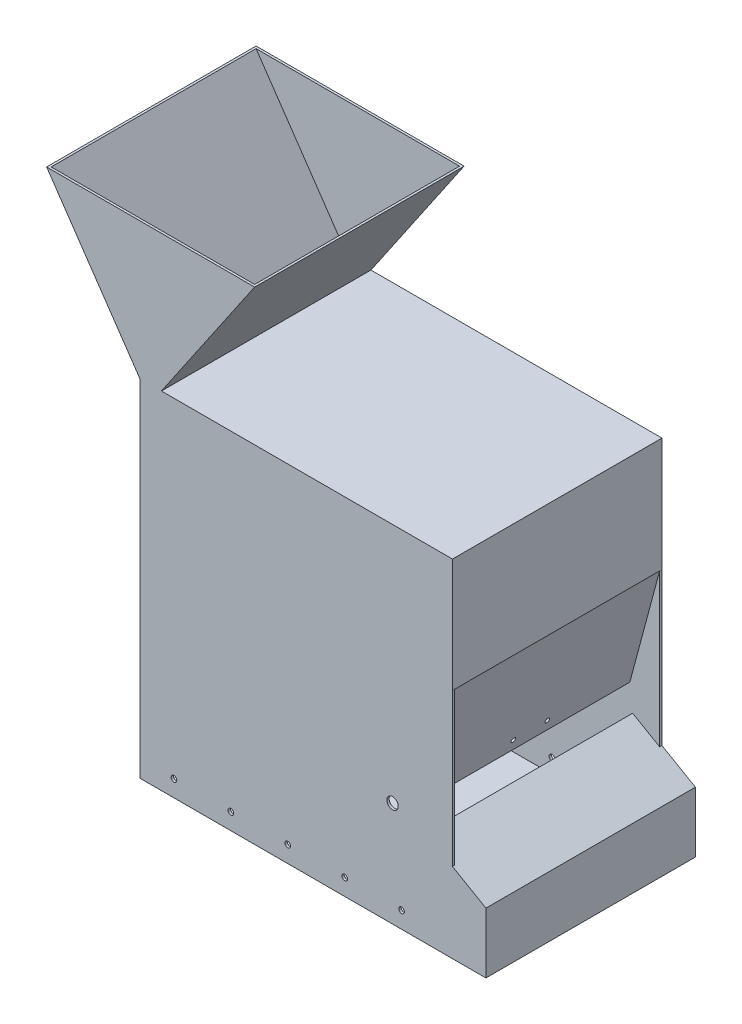
SolidWorks part; units mm, degrees
ref_plane "前视基准面" through (0, 0, 0) normal (0, 0, 1) x (1, 0, 0)
ref_plane "上视基准面" through (0, 0, 0) normal (0, 1, 0) x (1, 0, 0)
ref_plane "右视基准面" through (0, 0, 0) normal (1, 0, 0) x (0, 0, -1)
sketch "草图1" plane through (0, 0, 0) normal (0, 0, 1) x (1, 0, 0)
  line L0 (0, 0) -> (0, 200)
  line L1 (0, 200) -> (270, 200)
  line L3 (248.2424, 79.8823) -> (300, 50)
  line L4 (300, 50) -> (300, 0)
  line L5 (300, 0) -> (0, 0)
  line L7 (-2, 202) -> (272.6065, 202)
  line L9 (270, 200) -> (244.9779, 106.6164)
  line L10 (-2, 202) -> (-2, -2)
  line L11 (-2, -2) -> (302, -2)
  line L12 (302, -2) -> (302, 51.1547)
  line L13 (302, 51.1547) -> (248.8665, 81.8314)
  line L14 (272.6065, 202) -> (246.4095, 104.2316)
  circle A0 centre (220, 90) radius 30
  dimension "D6" = 60
  dimension "D1" = 300
  dimension "D2" = 200
  dimension "D3" = 50
  dimension "D4" = 30
  dimension "D5" = 270
  dimension "D7" = 110
  dimension "225" = 220
  dimension "D8" = 2
  dimension "D9" = 75
  dimension "D10" = 2
  dimension "D11" = 2
  dimension "D12" = 2
  dimension "D13" = 2
  dimension "D14" = 2
extrude "凸台-拉伸3" add sketch "草图1" along normal blind 180 contours A0 L7 L10 L11 L12 L13 L3 L4 L5 L0 L1 region at (150, -0.3661, 0)
sketch "草图7" plane through (0, 0, 0) normal (0, 0, -1) x (-1, 0, 0)
  line L1 (-302, 51.1547) -> (-248.8665, 81.8314) construction
  line L2 (-275.4332, 66.493) -> (-302, 51.1547)
  line L3 (-302, 51.1547) -> (-302, -2)
  line L4 (-302, -2) -> (2, -2)
  line L5 (2, -2) -> (2, 202)
  line L7 (2, 202) -> (-272.6065, 202)
  line L8 (-272.6065, 202) -> (-272.6065, 68.1251)
  line L9 (-272.6065, 68.1251) -> (-275.4332, 66.493)
extrude "凸台-拉伸4" add sketch "草图7" along normal blind 2
ref_plane "基准面3" through (0, 0, 90) normal (0, 0, 1) x (1, 0, 0)
mirror "镜向5" about plane through (0, 0, 90) normal (0, 0, 1) of "凸台-拉伸4"
sketch "草图8" plane through (0, 0, 0) normal (0, 0, 1) x (1, 0, 0)
  line L1 (-2, 202) -> (272.6065, 202) construction
  line L2 (-2, 202) -> (-2, -2) construction
  line L3 (-2, -2) -> (302, -2) construction
  line L4 (302, -2) -> (302, 51.1547) construction
  line L5 (302, 51.1547) -> (248.8665, 81.8314) construction
  line L7 (0, 200) -> (270, 200) construction
  line L8 (0, 0) -> (0, 200) construction
  line L9 (300, 0) -> (0, 0) construction
  line L10 (300, 50) -> (300, 0) construction
  line L11 (248.2424, 79.8823) -> (300, 50) construction
  line L13 (-2, 202) -> (272.6065, 202) construction
  line L14 (-2, 202) -> (-2, -2) construction
  line L15 (-2, -2) -> (302, -2) construction
  line L16 (302, -2) -> (302, 51.1547) construction
  line L17 (302, 51.1547) -> (248.8665, 81.8314) construction
  line L19 (0, 200) -> (270, 200)
  line L20 (0, 0) -> (0, 200) construction
  line L21 (300, 0) -> (0, 0) construction
  line L22 (300, 50) -> (300, 0) construction
  line L23 (248.2424, 79.8823) -> (300, 50) construction
  line L24 (220, 135.3561) -> (220, 31.0609) construction
  line L25 (165.6053, 90) -> (270, 90) construction
  line L26 (212.2354, 118.9778) -> (220, 90) construction
  line L27 (227.7646, 118.9778) -> (220, 90) construction
  line L28 (248.9778, 97.7646) -> (220, 90) construction
  line L29 (241.2132, 111.2132) -> (220, 90) construction
  line L30 (241.2132, 68.7868) -> (220, 90) construction
  line L31 (248.9778, 82.2354) -> (220, 90) construction
  line L32 (212.2354, 61.0222) -> (220, 90) construction
  line L33 (227.7646, 61.0222) -> (220, 90) construction
  line L34 (191.0222, 82.2354) -> (220, 90) construction
  line L35 (198.7868, 68.7868) -> (220, 90) construction
  line L36 (198.7868, 111.2132) -> (220, 90) construction
  line L37 (191.0222, 97.7646) -> (220, 90) construction
  line L38 (191.0222, 97.7646) -> (0, 144.3277)
  line L39 (0, 0) -> (0, 200) construction
  line L40 (0, 140.3998) -> (190.2705, 94.0199)
  line L41 (270, 200) -> (270.631, 202)
  line L42 (270.631, 202) -> (0, 202)
  line L43 (0, 202) -> (0, 200)
  circle A0 centre (220, 90) radius 30
  circle A1 centre (220, 90) radius 30
  circle A2 centre (220, 90) radius 30 construction
  point P36 (220, 90)
  line M26 (0, 200) -> (0, 0)
  dimension "D4" = 60
  dimension "D2" = 30
  dimension "D1" = 0
  dimension "D3" = 6
extrude "凸台-拉伸5" add sketch "草图8" along normal blind 180 contours A0 M26 region at (95.3036, 119.1341, 0)
sketch "草图10" plane through (0, 0, 0) normal (0, 0, 1) x (1, 0, 0)
  line L0 (300, 0) -> (0, 0) construction
  line L1 (0, 0) -> (0, 200) construction
  circle A0 centre (60, 60) radius 5
  circle A1 centre (95, 60) radius 6
  dimension "D1" = 10
  dimension "D4" = 35
  dimension "D5" = 12
  dimension "D2" = 60
  dimension "D3" = 60
extrude "切除-拉伸8" cut sketch "草图10" along normal blind 6 and the other way blind 14
extrude "切除-拉伸9" cut sketch "草图8<3>" along normal blind 180 contours L19 L41 L42 L43
sketch "草图8<3>" plane through (0, 0, 0) normal (0, 0, 1) x (1, 0, 0) same geometry as "草图8"
sketch "草图11" plane through (0, 202, 0) normal (0, 1, 0) x (1, 0, 0)
  line L0 (0, 0) -> (270.631, 0)
  line L1 (270.631, 0) -> (270.631, -180)
  line L2 (270.631, -180) -> (0, -180)
  line L3 (0, -180) -> (0, 0)
extrude "拉伸-薄壁1" add sketch "草图11" along normal blind 100 thin thin type one direction wall 2
sketch "草图12" plane through (0, 0, 180) normal (0, 0, -1) x (-1, 0, 0)
  line L0 (-15, 365.8341) -> (-15, 240.3517) construction
  line L1 (0, 144.3277) -> (0, 302) construction
  line L2 (-7.5, 359.5096) -> (-7.5, 254.5421) construction
  line L6 (-98.8691, 422) -> (-96.8691, 422)
  line L9 (-15, 302) -> (-96.8691, 422)
  line L10 (-272.631, 302) -> (2, 302) construction
  line L11 (-15, 302) -> (-17, 302)
  line L12 (-98.8691, 422) -> (-17, 302)
  line L13 (83.8691, 422) -> (81.8691, 422)
  line L14 (0, 302) -> (2, 302)
  line L15 (83.8691, 422) -> (2, 302)
  line L16 (0, 302) -> (81.8691, 422)
  dimension "D1" = 15
  dimension "D2" = 7.5
  dimension "D4" = 120
  dimension "D5" = 2
extrude "凸台-拉伸6" add sketch "草图12" along normal up to surface (90 mm away) and the other way blind 2 up to plane "基准面3"
ref_plane "基准面4" through (0, 0, 182) normal (0, 0, 1) x (1, 0, 0)
sketch "草图16" plane through (0, 0, 182) normal (0, 0, 1) x (1, 0, 0)
  line L0 (-83.8691, 422) -> (98.8691, 422)
  line L1 (98.8691, 422) -> (17, 302)
  line L2 (17, 302) -> (-2, 302)
  line L3 (-2, 302) -> (-83.8691, 422)
extrude "凸台-拉伸12" add sketch "草图16" against normal blind 2
mirror "镜向6" about plane through (0, 0, 90) normal (0, 0, 1) of "镜向5", "凸台-拉伸6"
mirror "镜向7" about plane through (0, 0, 90) normal (0, 0, 1) of "凸台-拉伸12"
sketch "草图17" plane through (0, 0, 180) normal (0, 0, -1) x (-1, 0, 0)
  line L0 (-15, 302) -> (-15, 252)
  line L1 (-15, 365.8341) -> (-15, 240.3517) construction
  line L2 (-15, 252) -> (-10, 232.2686)
  line L3 (-15, 302) -> (-17, 302)
  line L4 (-17, 300) -> (-17, 252)
  line L5 (-17, 252) -> (-11.9009, 231.8774)
  line L6 (-11.9009, 231.8774) -> (-10, 232.2686)
  line L7 (-17, 302) -> (-270.631, 302)
  line L8 (-270.631, 302) -> (-270.631, 300)
  line L9 (-270.631, 302) -> (-270.631, 202) construction
  line L10 (-270.631, 300) -> (-17, 300)
  dimension "D1" = 50
  dimension "D2" = 50
  dimension "D3" = 5
  dimension "D4" = 2
extrude "凸台-拉伸13" add sketch "草图17" along normal blind 180
sketch "草图19" plane through (0, 0, 0) normal (0, 0, 1) x (1, 0, 0)
  line L0 (0, 0) -> (0, 140.3998) construction
  line L1 (300, 0) -> (0, 0) construction
  circle A0 centre (60, 60) radius 5
  circle A1 centre (95, 60) radius 6
  circle A2 centre (220, 90) radius 5
  dimension "D1" = 10
  dimension "D4" = 12
  dimension "D6" = 10
  dimension "D2" = 60
  dimension "D3" = 60
  dimension "D5" = 35
extrude "切除-拉伸10" cut sketch "草图19" against normal blind 10
sketch "草图20" plane through (0, 0, 180) normal (0, 0, -1) x (-1, 0, 0)
  circle A0 centre (-220, 90) radius 5 construction
  circle A1 centre (-220, 90) radius 5
extrude "切除-拉伸11" cut sketch "草图20" against normal blind 10
sketch "草图21" plane through (203.8453, -54.6202, 0) normal (0.9659, -0.2588, 0) x (0, 0, -1)
  line L0 (-90, 165) -> (-90, -165) construction
  line L1 (-180, 164.4555) -> (0, 164.4555) construction
  circle A0 centre (-105, 174.4555) radius 2
  circle A1 centre (-75, 174.4555) radius 2
  dimension "D1" = 4
  dimension "D2" = 15
  dimension "D3" = 10
extrude "切除-拉伸12" cut sketch "草图21" against normal blind 10
sketch "草图22" plane through (0, 0, 0) normal (0, 0, 1) x (1, 0, 0)
  line L0 (3.6413, 25) -> (99.8808, 25) construction
  line L1 (-2, -2) -> (302, -2) construction
  line L2 (-2, 202) -> (-2, -2) construction
  circle A0 centre (28, 12.5) radius 2.5
  circle A1 centre (78, 12.5) radius 2.5
  circle A2 centre (128, 12.5) radius 2.5
  circle A3 centre (178, 12.5) radius 2.5
  circle A4 centre (228, 12.5) radius 2.5
  dimension "D1" = 5
  dimension "D2" = 12.5
  dimension "D3" = 27
  dimension "D5" = 30
  dimension "D4" = 5
extrude "切除-拉伸13" cut sketch "草图22" against normal through all and the other way through all
